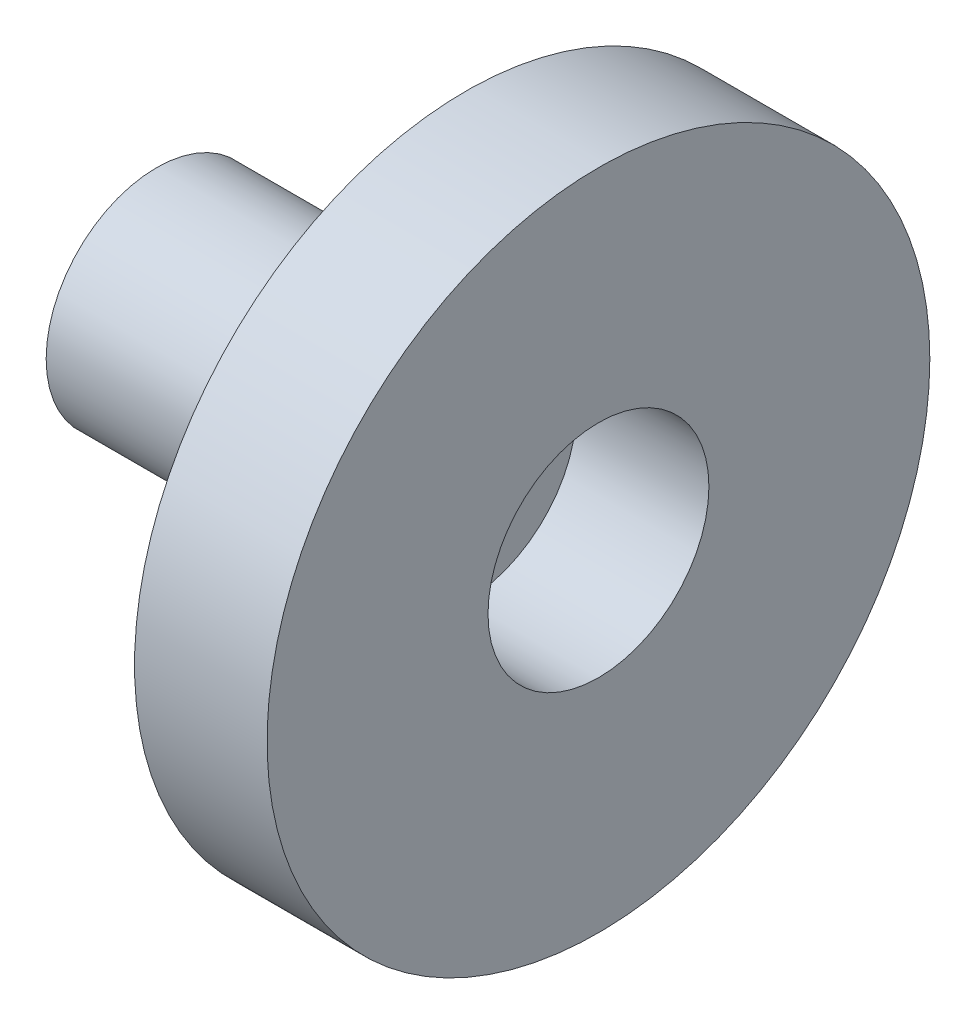
SolidWorks part; units mm, degrees
ref_plane "Ön Düzlem" through (0, 0, 0) normal (0, 0, 1) x (1, 0, 0)
ref_plane "Üst Düzlem" through (0, 0, 0) normal (0, 1, 0) x (1, 0, 0)
ref_plane "Sağ Düzlem" through (0, 0, 0) normal (1, 0, 0) x (0, 0, -1)
sketch "Çizim1" plane through (0, 0, 0) normal (1, 0, 0) x (0, 0, -1)
  circle A0 centre (0, 0) radius 15
extrude "Yükseklik-Ekstrüzyon1" add sketch "Çizim1" along normal blind 6
sketch "Çizim2" plane through (0, 0, 0) normal (-1, 0, 0) x (0, 0, 1)
  circle A0 centre (0, 0) radius 5
  dimension "D1" = 10
sketch "Çizim4" plane through (0, 0, 0) normal (-1, 0, 0) x (0, 0, 1)
  circle A0 centre (0, 0) radius 6
extrude "Kes-Ekstrüzyon2" cut sketch "Çizim4" against normal blind 14 and the other way blind 14
extrude "Yükseklik-Ekstrüzyon2" add sketch "Çizim2" along normal blind 14 separate body
sketch "Çizim5" plane through (6, 0, 0) normal (1, 0, 0) x (0, 0, -1)
  circle A0 centre (0, 0) radius 6
  circle A1 centre (0, 0) radius 5
extrude "Yükseklik-Ekstrüzyon3" add sketch "Çizim5" against normal up to surface (6 mm away) up to face at (0, 0, -6)
